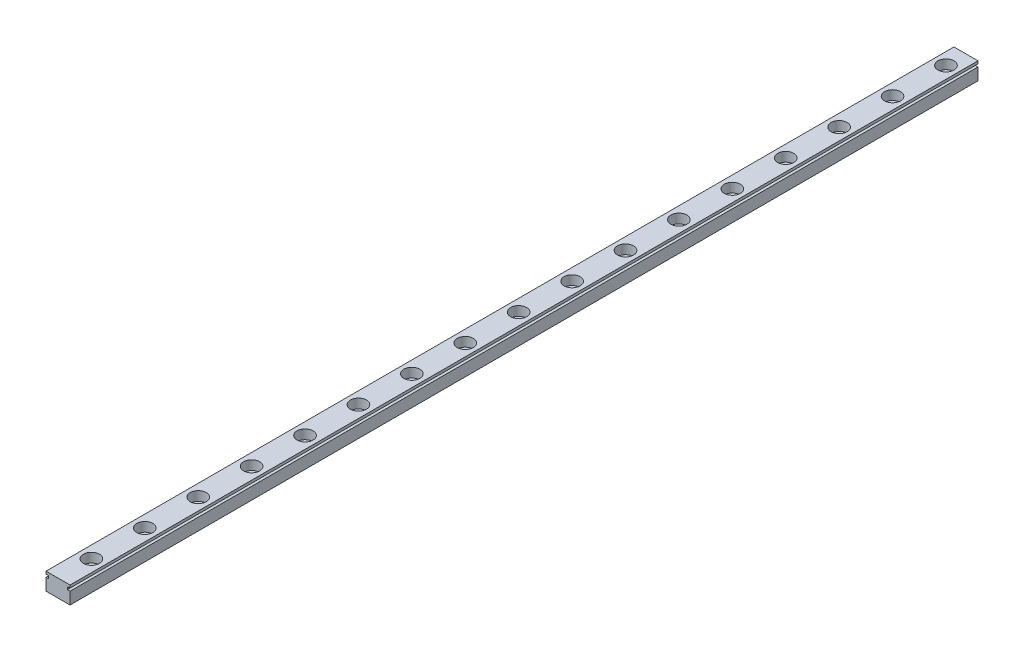
SolidWorks part; units mm, degrees
material "1.0401 (C15)"
ref_plane "前视基准面" through (0, 0, 0) normal (0, 0, 1) x (1, 0, 0)
ref_plane "上视基准面" through (0, 0, 0) normal (0, 1, 0) x (1, 0, 0)
ref_plane "右视基准面" through (0, 0, 0) normal (1, 0, 0) x (0, 0, -1)
sketch "草图1" plane through (0, 0, 0) normal (0, 0, 1) x (1, 0, 0)
  line L0 (0, -0.8589) -> (0, 7.8911) construction
  line L1 (-4.5, 0) -> (4.5, 0)
  line L2 (4.5, 0) -> (4.5, 4.5)
  line L3 (4.5, 5.5) -> (3.5, 5.5)
  line L4 (3.5, 5.5) -> (3.5, 4.5)
  line L5 (4.5, 5.5) -> (4.5, 6.5)
  line L6 (4.5, 6.5) -> (-4.5, 6.5)
  line L7 (3.5, 4.5) -> (4.5, 4.5)
  line L8 (-4.5, 0) -> (-4.5, 4.5)
  line L9 (-3.5, 4.5) -> (-4.5, 4.5)
  line L10 (-3.5, 5.5) -> (-3.5, 4.5)
  line L11 (-4.5, 5.5) -> (-3.5, 5.5)
  line L12 (-4.5, 5.5) -> (-4.5, 6.5)
  point P12 (0, 0)
  point P17 (0, 6.5)
  dimension "D1" = 4.5
  dimension "D2" = 6.5
  dimension "D3" = 1
  dimension "D4" = 1
  dimension "D5" = 1
  dimension "D6" = 4.5
extrude "凸台-拉伸1" add sketch "草图1" along normal blind 340
sketch "草图2" plane through (0, 0, 0) normal (1, 0, 0) x (0, 0, -1)
  line L0 (-7.5, 7.6159) -> (-7.5, -2.728) construction
  line L1 (-7.5, 0) -> (-6, 0)
  line L2 (-340, 0) -> (0, 0) construction
  line L3 (-6, 0) -> (-6, 3)
  line L4 (-6, 3) -> (-4.5, 3)
  line L5 (-4.5, 3) -> (-4.5, 6.5)
  line L6 (-340, 6.5) -> (0, 6.5) construction
  line L7 (-4.5, 6.5) -> (-7.5, 6.5)
  line L8 (-7.5, 0) -> (-7.5, 6.5)
  dimension "D1" = 7.5
  dimension "D2" = 1.5
  dimension "D3" = 3
  dimension "D4" = 3.5
revolve "切除-旋转1" cut sketch "草图2" angle 360 about L0
pattern_linear "阵列(线性)1" count 17 spacing 20 along (0, 0, 1) of "切除-旋转1"
